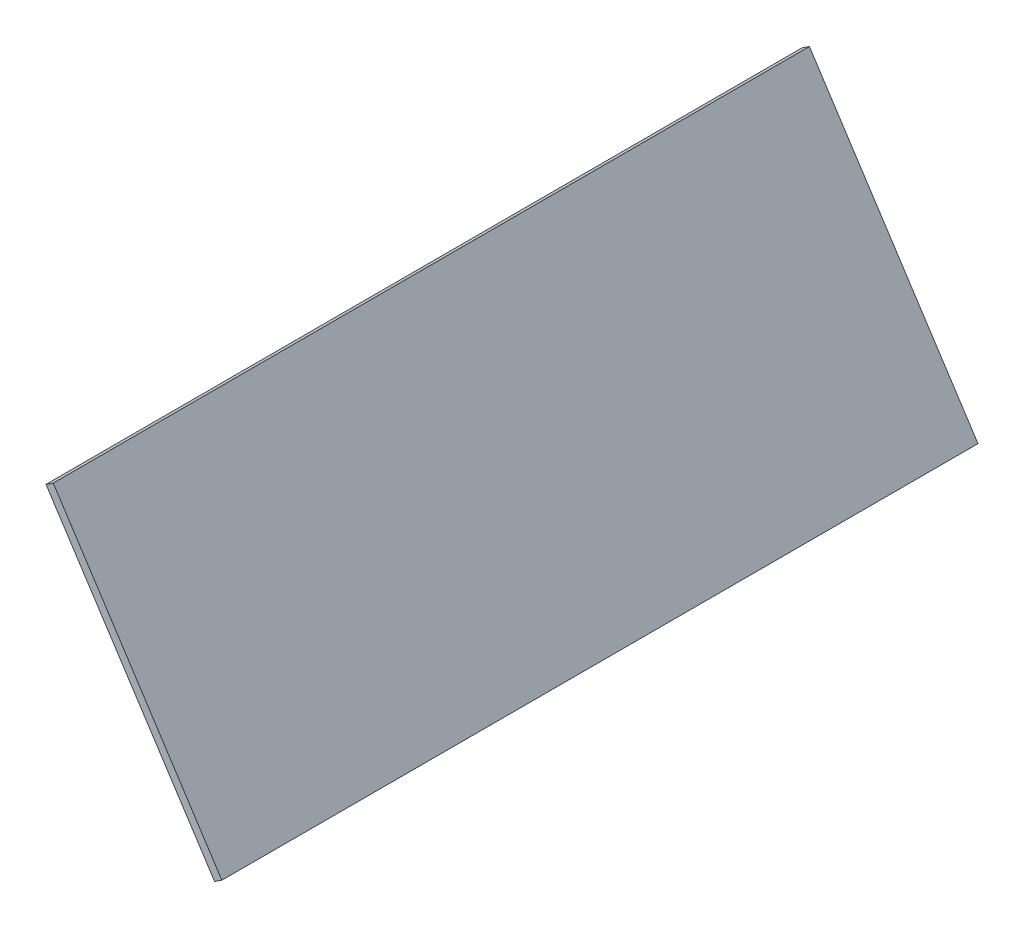
SolidWorks part; units mm, degrees
material "5052-H34"
ref_plane "Front Plane" through (0, 0, 0) normal (0, 0, 1) x (1, 0, 0)
ref_plane "Top Plane" through (0, 0, 0) normal (0, 1, 0) x (1, 0, 0)
ref_plane "Right Plane" through (0, 0, 0) normal (1, 0, 0) x (0, 0, -1)
sketch "Sketch1" plane through (0, 0, 0) normal (0, 0, 1) x (1, 0, 0)
  line L16 (-207.8332, 9.5074) -> (-145.9622, -85.7656)
  line L17 (-210.496, 7.7781) -> (-148.625, -87.4948)
  line L18 (-148.625, -87.4948) -> (-145.9622, -85.7656)
  line L19 (-207.8332, 9.5074) -> (-210.496, 7.7781)
  point P0 (-199.8594, 9.5074)
  dimension "D2" = 3.175
  dimension "D3" = 113.6
extrude "Boss-Extrude1" add sketch "Sketch1" along normal blind 277.48 contours L16 L18 L17 L19
